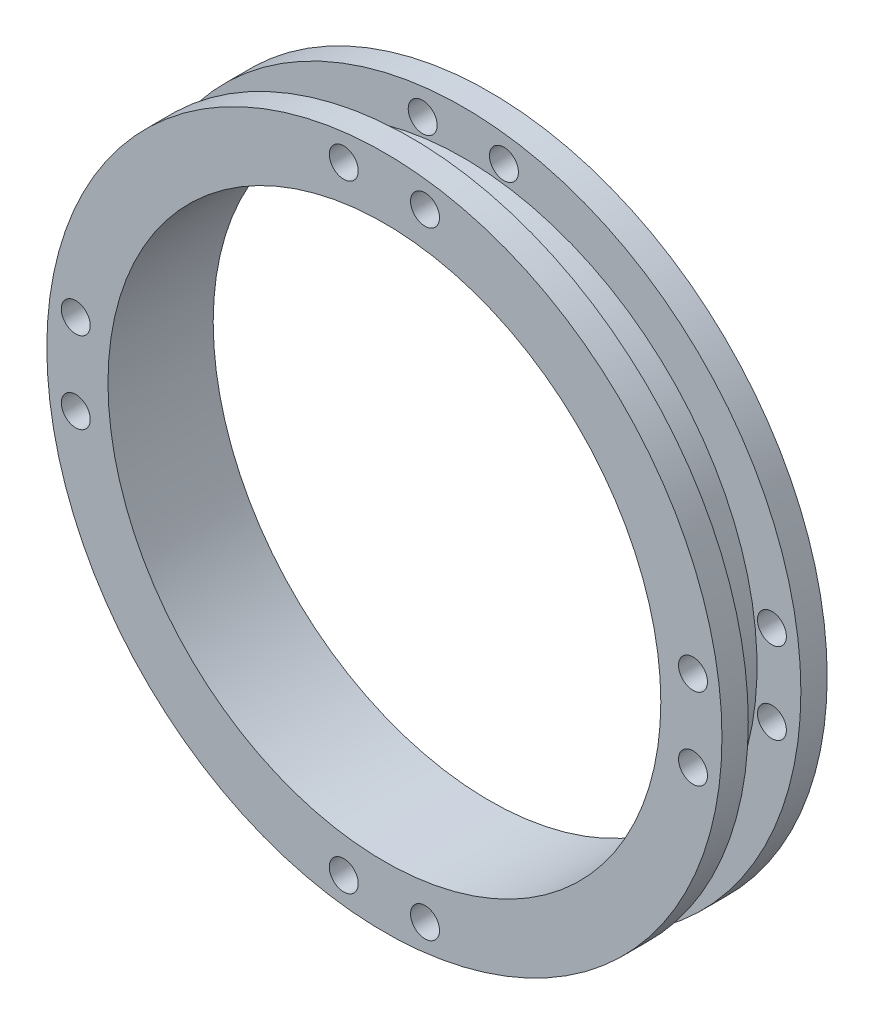
SolidWorks part; units mm, degrees
material "6063-O"
ref_plane "Front" through (0, 0, 0) normal (0, 0, 1) x (1, 0, 0)
ref_plane "Top" through (0, 0, 0) normal (0, 1, 0) x (1, 0, 0)
ref_plane "Right" through (0, 0, 0) normal (1, 0, 0) x (0, 0, -1)
sketch "Sketch1" plane through (0, 0, 0) normal (0, 0, 1) x (1, 0, 0)
  circle A0 centre (0, 0) radius 31.5
  circle A1 centre (0, 0) radius 33.5
  dimension "D1" = 2
  dimension "`" = 63
extrude "Boss-Extrude1" add sketch "Sketch1" along normal blind 9
extrude "Boss-Extrude2" add sketch "Sketch1<2>" against normal blind 3 contours A0 | A1 A0 region at (0, 0, 0) region at (-32.5525, 0, 0)
sketch "Sketch1<2>" plane through (0, 0, 0) normal (0, 0, 1) x (1, 0, 0) same geometry as "Sketch1"
sketch "Sketch2" plane through (0, 0, -3) normal (0, 0, -1) x (-1, 0, 0)
  circle A0 centre (0, 0) radius 33.5
  circle A1 centre (0, 0) radius 38.5
  dimension "D1" = 5
extrude "Boss-Extrude3" add sketch "Sketch2" against normal blind 3
sketch "Sketch3" plane through (0, 0, 9) normal (0, 0, 1) x (1, 0, 0)
  circle A0 centre (0, 0) radius 33.5
  circle A1 centre (0, 0) radius 38.5
  dimension "D1" = 77
extrude "Boss-Extrude4" add sketch "Sketch3" against normal blind 3
sketch "Sketch10" plane through (0, 0, -3) normal (0, 0, -1) x (-1, 0, 0)
  circle A0 centre (0, 0) radius 11 construction
  circle A1 centre (0, 11) radius 2
  circle A2 centre (11, 0) radius 2
  circle A3 centre (0, -11) radius 2
  circle A4 centre (-11, 0) radius 2
  point P14 (0, 0)
  dimension "D1" = 22
  dimension "D2" = 4
  dimension "D3" = 4
extrude "Cut-Extrude1" cut sketch "Sketch10" against normal blind 10
sketch "Sketch11" plane through (0, 0, -3) normal (0, 0, -1) x (-1, 0, 0)
  line L0 (0, 0) -> (0, 35.5) construction
  line L1 (0, 0) -> (-4.6337, 35.1963) construction
  line L2 (0, 0) -> (4.6337, 35.1963) construction
  circle A0 centre (0, 0) radius 35.5 construction
  dimension "D1" = 71
  dimension "D2" = 7.5
  dimension "D3" = 7.5
hole_wizard "M4 Tapped Hole1" positions "Sketch13" profile "Sketch12" tap size "M4" standard "ISO" end condition through all
sketch "Sketch13" plane through (0, 0, -3) normal (0, 0, -1) x (-1, 0, 0)
  point P0 (-4.6337, 35.1963)
  point P3 (4.6337, 35.1963)
sketch "Sketch12" plane through (4.6337, 35.1963, -3) normal (1, 0, 0) x (0, 1, 0)
  line L0 (0, 0) -> (0, 12)
  line L1 (0, 12) -> (1.65, 12)
  line L2 (1.65, 12) -> (1.65, 0)
  line L5 (1.65, 0) -> (0, 0)
  line L11 (0, -6.35) -> (0, 107.95) construction
  dimension "Thru Tap Drill Dia." = 3.3
  dimension "Thru Tap Drill Depth" = 12
cosmetic thread "Hole Thread3" parameters "D2"=4
cosmetic thread "Hole Thread4" parameters "D2"=4
pattern_circular "CirPattern1" count 4 over 360 about axis through (0, 0, 9) along (0, 0, -1) of "M4 Tapped Hole1"
sketch "Sketch14" plane through (0, 0, 0) normal (0, 0, 1) x (1, 0, 0)
  circle A0 centre (0, 0) radius 31.525
  dimension "D1" = 63.05
extrude "Cut-Extrude2" cut sketch "Sketch14" along normal through all
sketch "Sketch15" plane through (0, 0, -3) normal (0, 0, -1) x (-1, 0, 0)
  circle A0 centre (0, 0) radius 31.525
  dimension "D1" = 63.05
extrude "Cut-Extrude3" cut sketch "Sketch15" against normal blind 10
